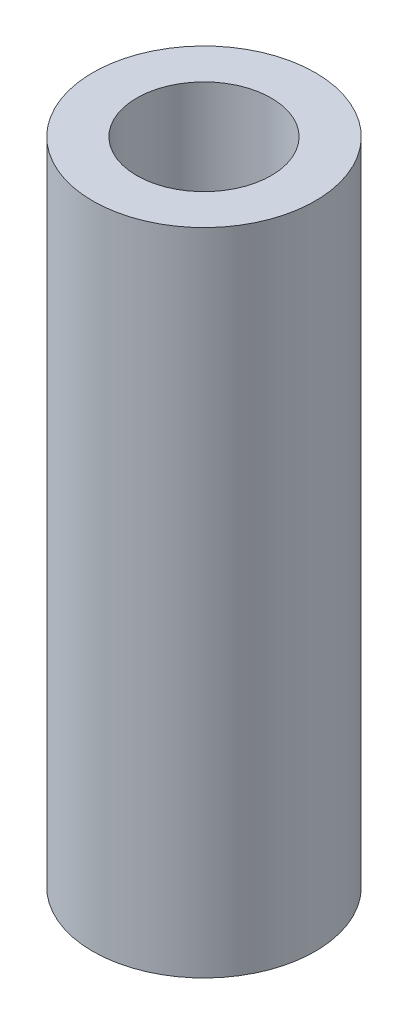
SolidWorks part; units mm, degrees
ref_plane "Front Plane" through (0, 0, 0) normal (0, 0, 1) x (1, 0, 0)
ref_plane "Top Plane" through (0, 0, 0) normal (0, 1, 0) x (1, 0, 0)
ref_plane "Right Plane" through (0, 0, 0) normal (1, 0, 0) x (0, 0, -1)
sketch "Sketch1" plane through (0, 0, 0) normal (0, 1, 0) x (1, 0, 0)
  circle A0 centre (0, 0) radius 7.5
  dimension "SLEEVE_OD" = 15
extrude "Boss-Extrude1" add sketch "Sketch1" along normal blind 43.8228
sketch "Sketch2" plane through (0, 0, 0) normal (0, 1, 0) x (1, 0, 0)
  circle A0 centre (0, 0) radius 4.5353
  dimension "BORE_D" = 9.0706
extrude "Cut-Extrude1" cut sketch "Sketch2" along normal through all
chamfer "Chamfer1" distance 1.492 angle 45 rebuild error yes
